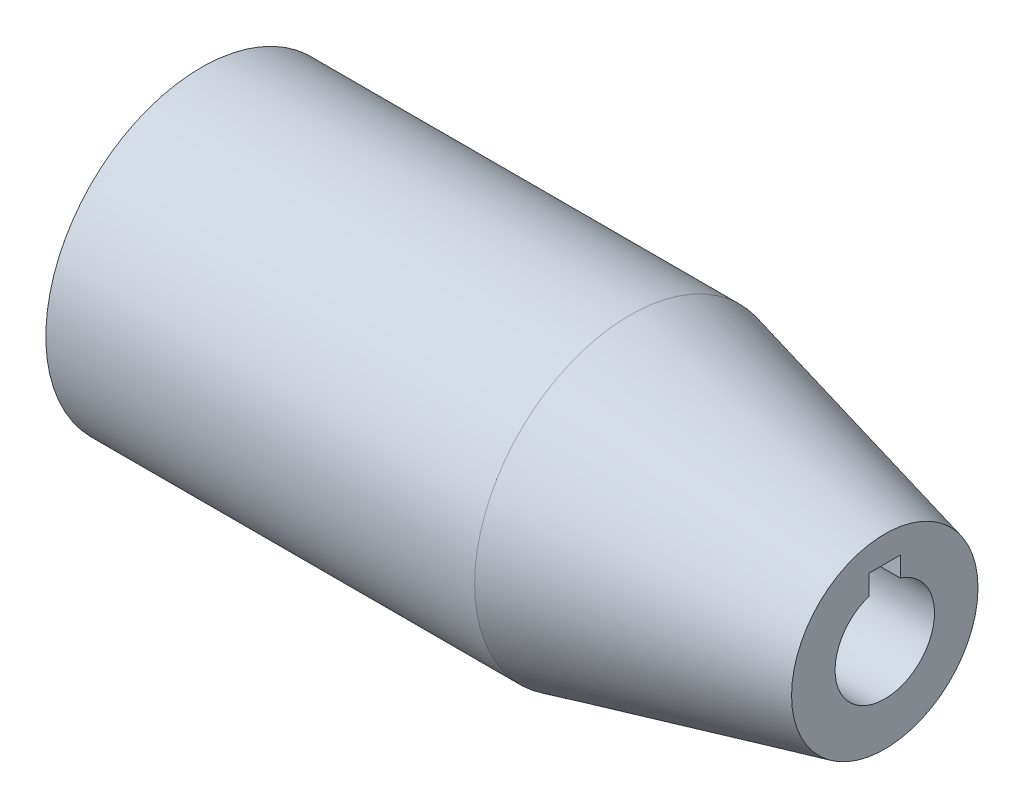
SolidWorks part; units mm, degrees
ref_plane "Спереди" through (0, 0, 0) normal (0, 0, 1) x (1, 0, 0)
ref_plane "Сверху" through (0, 0, 0) normal (0, 1, 0) x (1, 0, 0)
ref_plane "Справа" through (0, 0, 0) normal (1, 0, 0) x (0, 0, -1)
sketch "Эскиз2" plane through (0, 0, 0) normal (1, 0, 0) x (0, 0, -1)
  line L1 (0, 5) -> (2.5, 5)
  line L2 (0, 5) -> (-2.5, 5)
  line L4 (0, 10.8) -> (2.5, 10.8)
  line L5 (2.5, 10.8) -> (2.5, 5)
  line L6 (0, 10.8) -> (-2.5, 10.8)
  line L7 (-2.5, 10.8) -> (-2.5, 5)
  circle A0 centre (0, 0) radius 8
  circle A1 centre (0, 0) radius 15
  point P4 (0, 8)
  point P5 (0, 8)
  point P6 (0, 8)
  point P7 (0, 8)
  dimension "D1" = 16
  dimension "D2" = 30
extrude "Бобышка-Вытянуть2" add sketch "Эскиз2" along normal blind 41 contours A1 A0 L4 L5 region at (0, 0, 14.5757)
sketch "Эскиз5" plane through (0, 0, 0) normal (1, 0, 0) x (0, 0, -1)
  circle A0 centre (0, 0) radius 25
extrude "Бобышка-Вытянуть4" add sketch "Эскиз5" against normal blind 9
sketch "Эскиз6" plane through (0, 0, 0) normal (1, 0, 0) x (0, 0, -1)
  line L1 (0, 10) -> (-4, 10)
  line L2 (0, 10) -> (4, 10)
  line L4 (0, 17.3) -> (-4, 17.3)
  line L5 (-4, 17.3) -> (-4, 10)
  line L6 (0, 17.3) -> (4, 17.3)
  line L7 (4, 17.3) -> (4, 10)
  circle A0 centre (0, 0) radius 25
  circle A1 centre (0, 0) radius 14
extrude "Бобышка-Вытянуть5" add sketch "Эскиз6" against normal blind 60 from offset 9 contours A0 A1 L5 L4 L6 L7 region at (0, 0, 24.2929) offset against normal yes
sketch "Эскиз7" plane through (0, 0, 0) normal (0, 1, 0) x (1, 0, 0)
  line L0 (0, 25) -> (0, 15)
  line L1 (0, 15) -> (41, 15)
  line L2 (41, 15) -> (0, 25)
  line L3 (0, 25) -> (0.1285, 24.9716)
  line L5 (-60.1971, 0) -> (0, 0)
revolve "Повернуть1" add sketch "Эскиз7" angle 360 about L5 region at (13.6667, 0, -18.3333)
